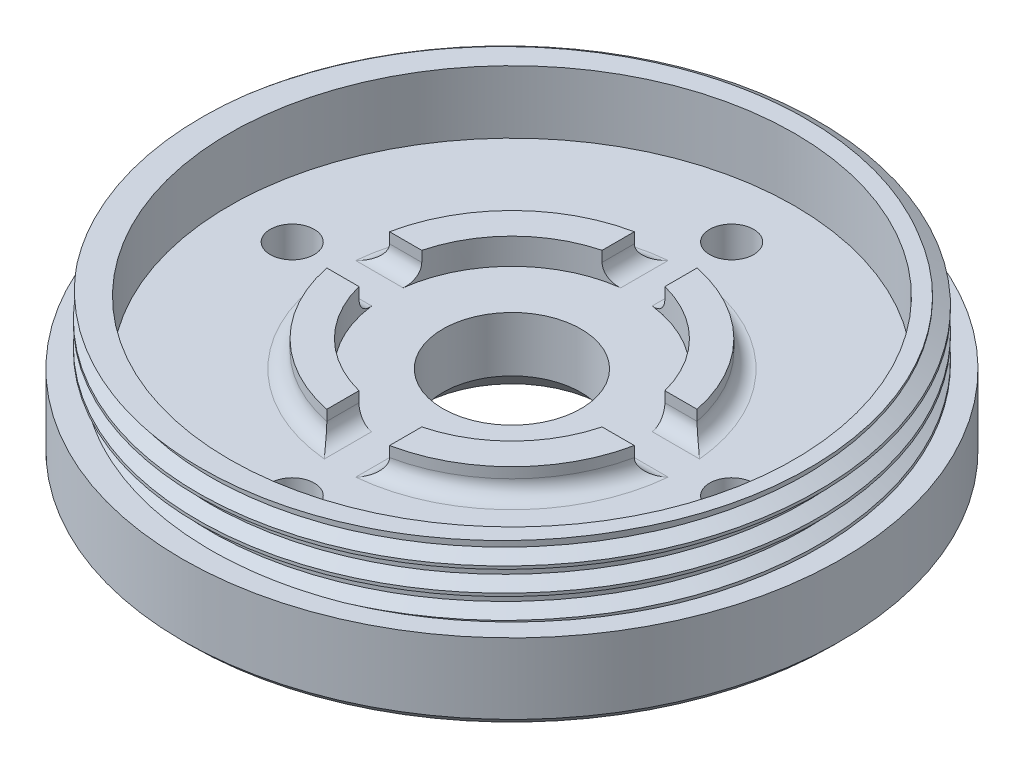
SolidWorks part; units mm, degrees
ref_plane "Front plane" through (0, 0, 0) normal (0, 0, 1) x (1, 0, 0)
ref_plane "Top plane" through (0, 0, 0) normal (0, 1, 0) x (1, 0, 0)
ref_plane "Right plane" through (0, 0, 0) normal (1, 0, 0) x (0, 0, -1)
ref_axis "Axis X" through (0, 0, 0) along (1, 0, 0)
ref_axis "Axis Y" through (0, 0, 0) along (0, 1, 0)
ref_axis "Axis Z" through (0, 0, 0) along (0, 0, 1)
sketch "Sketch1" plane through (0, 0, 0) normal (0, 1, 0) x (1, 0, 0)
  circle A0 centre (0, 0) radius 21
  circle A1 centre (0, 0) radius 4.4
  circle A2 centre (0, 0) radius 14 construction
  circle A3 centre (0, 14) radius 1.4
  circle A4 centre (14, 0) radius 1.4
  circle A5 centre (0, -14) radius 1.4
  circle A6 centre (-14, 0) radius 1.4
  point P16 (0, 0)
  dimension "D1" = 42
  dimension "D2" = 8.8
  dimension "D3" = 28
  dimension "D4" = 2.8
  dimension "D5" = 4
extrude "Extrude1" add sketch "Sketch1" along normal blind 5
sketch "Sketch8" plane through (0, 5, 0) normal (0, 1, 0) x (1, 0, 0)
  circle A1 centre (0, 0) radius 18
  circle A3 centre (0, 0) radius 18.95
  dimension "D1" = 36
  dimension "D2" = 0.95
extrude "Бобышка-Вытянуть1" add sketch "Sketch8" along normal blind 4
thread "Резьба1" pitch 1.5 method extrude trim with start face yes trim with end face yes profile "Профиль резьбы1" start angle 0, offset 2, length 0, pitch 1.5, diameter 37.9
ref_plane "Плоскость1" through (-18.95, 11, 0) normal (0, 0, 1) x (-1, 0, 0)
sketch "Профиль резьбы1" plane through (-18.95, 11, 0) normal (0, 0, 1) x (-1, 0, 0)
  line L0 (0, 0) -> (0, 1.5) construction
  line L1 (0, 0) -> (0.8119, 0.4687)
  line L2 (0.8119, 0.4687) -> (0.8119, 0.6562)
  line L3 (0.8119, 0.6562) -> (0, 1.125)
  line L4 (0.8119, 0.5625) -> (0, 0.5625) construction
  line L11 (0, 0) -> (0, 1.125)
  point P2 (0, 0)
  dimension "Pitch" = 1.5
  dimension "Profile_Angle" = 60
  dimension "Profile_Land" = 0.1875
  dimension "Profile_Height" = 0.8119
sketch "Эскиз3" plane through (0, 5, 0) normal (0, 1, 0) x (1, 0, 0)
  line L0 (0, 0) -> (0, 10) construction
  line L1 (-2, 9.798) -> (-2, 7.746)
  line L2 (2, 9.798) -> (2, 7.746)
  line L3 (9.798, 2) -> (7.746, 2)
  line L4 (9.798, -2) -> (7.746, -2)
  line L5 (2, -9.798) -> (2, -7.746)
  line L6 (-2, -9.798) -> (-2, -7.746)
  line L7 (-9.798, -2) -> (-7.746, -2)
  line L8 (-9.798, 2) -> (-7.746, 2)
  arc A0 (-2, 7.746) -> (-7.746, 2) centre (0, 0) ccw
  arc A1 (-2, 9.798) -> (-9.798, 2) centre (0, 0) ccw
  arc A2 (7.746, 2) -> (2, 7.746) centre (0, 0) ccw
  arc A3 (9.798, 2) -> (2, 9.798) centre (0, 0) ccw
  arc A4 (-7.746, -2) -> (-2, -7.746) centre (0, 0) ccw
  arc A5 (-9.798, -2) -> (-2, -9.798) centre (0, 0) ccw
  arc A6 (2, -7.746) -> (7.746, -2) centre (0, 0) ccw
  arc A7 (2, -9.798) -> (9.798, -2) centre (0, 0) ccw
  dimension "D1" = 16
  dimension "D2" = 2
  dimension "D3" = 4
  dimension "D4" = 4
extrude "Бобышка-Вытянуть2" add sketch "Эскиз3" along normal blind 1.6667
fillet "Скругление1" radius 1 12 edges at (-2, 5, -8.772) (2, 5, -8.772) (7.0711, 5, -7.0711) (8.772, 5, -2) (8.772, 5, 2) (7.0711, 5, 7.0711) (-7.0711, 5, -7.0711) (-7.0711, 5, 7.0711) (2, 5, 8.772) (-2, 5, 8.772) (-8.772, 5, 2) (-8.772, 5, -2)
chamfer "Chamfer2" distance 1.5 angle 45 1 edges at (0, 0, 4.4)
chamfer "Chamfer3" distance 0.5 angle 45 1 edges at (0, 0, 21)
chamfer "Chamfer4" distance 1 angle 45 4 edges at (0, 0, -12.6) (14, 0, 1.4) (-14, 0, 1.4) (0, 0, 15.4)
equation "\"motor_D\"= 34'Motor diameter"
equation "\"motor_H\"= 16'Motor heigh"
equation "\"motor_d1\"= 30.4056'Seating diameter of screws on the fixed part of the motor"
equation "\"motor_s1\"= 2'Screws diameter on the fixed part of motor"
equation "\"motor_a2\"= 12'Seating parameter in rectangle of screws on the moving part of the motor"
equation "\"motor_s2\"= 2.5'Screws diameter on the moving part of motor"
equation "\"motor_Dc\"= 5'Central hole diameter of motor"
equation "\"bearing_d1\"= 8'Bearing inner diameter"
equation "\"bearing_d2\"= 16'Bearing external diameter"
equation "\"bearing h\"= 5'Bearing heigh"
equation "\"pin_d\"= 2'Pin diameter"
equation "\"pin_h\"= 12'Pin heigh"
equation "\"magnet_d1\"= 5'Magnet inner diameter"
equation "\"magnet_d2\"= 9.5'Magnet external diameter"
equation "\"magnet_h\"= 3'Magnet heigh"
equation "\"motor_b2\"= 22'Seating parameter in rectangle of screws on the moving part of the motor"
equation "\"motor_d2\"= 0'Seating diameter of screws on the moving part of the motor (if this parameter is not determine, write 0)"
equation "\"motor_cmd\"= 12'Central magnet mount diameter"
equation "\"motor_cmh\"= 0.4'Central magnet mount heigh (if not write 0)"
equation "\"motor_whR\"= 10'Distance from center of motor to wires"
equation "\"D1@Sketch1\"= IIF ( \"motor_D\" < 34 , 41 , \"motor_D\" + 8 )"
equation "\"D2@Sketch1\"=\"ft_sensor_d1\"-1"
equation "\"D4@Sketch1\"=3-\"print_offset\""
equation "\"print_offset\"= 0.2'Offset for printing holes"
equation "\"ft_sensor_d1\"= 9.8"
equation "\"ft_sensor_d2\"= 24.9"
equation "\"ft_sensor_d3\"= 22.6'Inner diameter of "
equation "\"ft_sensor_h\"= 7.1"
equation "\"ft_sensor_whD\" = 5"
equation "\"D1@Sketch8\" = IIF ( \"motor_D\" < 34 , 41 , \"motor_D\" + 8 ) - 6"
equation "\"D2@Sketch8\"= 0.95"
equation "\"D1@Эскиз3\"=\"bearing_d2\""
equation "\"D1@Бобышка-Вытянуть2\"=\"bearing h\"/3"
